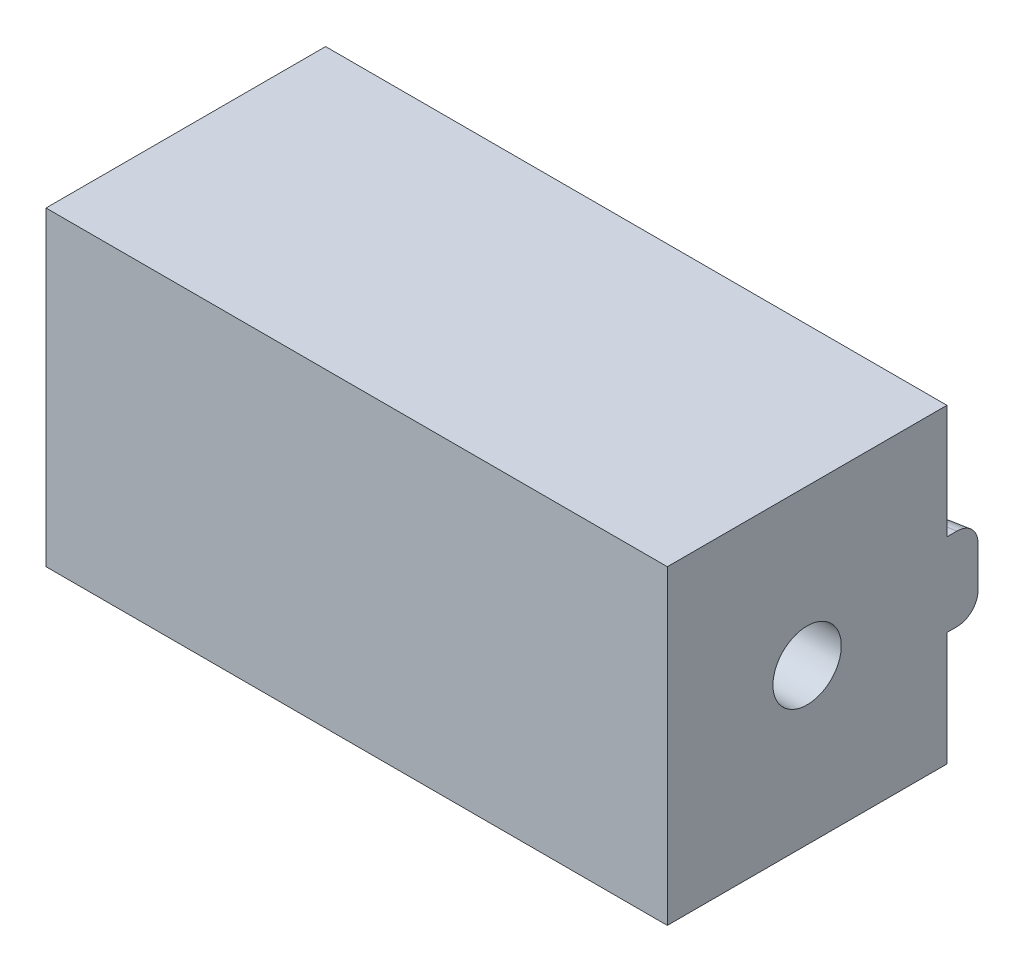
SolidWorks part; units mm, degrees
ref_plane "Top Plane" through (0, 0, 0) normal (0, 0, 1) x (1, 0, 0)
ref_plane "Right Plane" through (0, 0, 0) normal (0, 1, 0) x (1, 0, 0)
ref_plane "Front Plane" through (0, 0, 0) normal (1, 0, 0) x (0, 0, -1)
sketch "Sketch1" plane through (0, 0, 0) normal (0, 0, 1) x (1, 0, 0)
  line L1 (0, -7.5) -> (30, -7.5)
  line L2 (0, -7.5) -> (0, 7.5)
  line L3 (0, 7.5) -> (30, 7.5)
  line L4 (30, -7.5) -> (30, 7.5)
  dimension "D1" = 30
  dimension "D2" = 15
extrude "Boss-Extrude1" add sketch "Sketch1" along normal mid plane 13.5
sketch "Sketch2" plane through (0, 0, 0) normal (0, 1, 0) x (1, 0, 0)
  line L12 (0, 0) -> (30, 0) construction
  line L14 (30, 0) -> (30, 6.75) construction
  line L20 (0, 0) -> (30, 0)
  line L21 (0, 0) -> (0, 3)
  line L22 (0, 3) -> (22.5, 3)
  line L23 (22.5, 1.65) -> (22.5, 3)
  line L25 (30, 0) -> (30, 1.65)
  line L26 (30, 1.65) -> (22.5, 1.65)
  dimension "D1" = 7.5
  dimension "D2" = 3
  dimension "D3" = 1.65
sketch "Sketch3" plane through (0, -7.5, 0) normal (0, -1, 0) x (1, 0, 0)
  line L0 (0, 0) -> (30, 0) construction
  line L1 (0, 6.75) -> (0, -6.75) construction
  line L2 (30, 6.75) -> (30, -6.75) construction
  circle A0 centre (8, 0) radius 1.5
  circle A1 centre (23, 0) radius 1.5
  dimension "D1" = 3
  dimension "D2" = 7
  dimension "D3" = 15
extrude "Cut-Extrude1" cut sketch "Sketch3" against normal blind 3
sketch "Sketch4" plane through (0, 0, 0) normal (0, 1, 0) x (1, 0, 0)
  line L0 (30, 6.75) -> (30, 8.25)
  line L1 (30, 8.25) -> (22, 6.75)
  line L2 (22, 6.75) -> (30, 6.75)
  dimension "D1" = 15
  dimension "D2" = 8
extrude "Boss-Extrude2" add sketch "Sketch4" along normal mid plane 4
fillet "Fillet1" radius 1 2 edges at (26, 2, -7.5) (26, -2, -7.5)
revolve "Cut-Revolve1" cut sketch "Sketch2" angle 360 about L20
sketch "Sketch5" [suppressed] plane through (0, 0, 0) normal (0, 1, 0) x (1, 0, 0)
  line L0 (8.8, 3) -> (30, 3)
  line L1 (0, 0) -> (57, 0)
  line L2 (0, 0) -> (0, 3)
  line L3 (0, 3) -> (8.2, 3)
  line L4 (35, 1.5) -> (30, 3)
  line L7 (35, 1.5) -> (52, 1.5)
  line L8 (57, 0) -> (57, 1.3)
  line L11 (57, 1.3) -> (52, 1.3)
  line L12 (52, 1.5) -> (52, 1.3)
  arc A0 (8.8, 3) -> (8.2, 3) centre (8.5, 3) cw
  dimension "D7" = 0.3
  dimension "D1" = 3
  dimension "D2" = 57
  dimension "D3" = 30
  dimension "D4" = 1.5
  dimension "D5" = 0.2
  dimension "D6" = 5
  dimension "D8" = 8.5
  dimension "D9" = 22
revolve "Revolve1" [suppressed] add sketch "Sketch5" angle 360 about L1
fillet "Fillet2" [suppressed] radius 0.5
sketch "Sketch6" [suppressed] plane through (0, 0, 0) normal (0, 1, 0) x (1, 0, 0)
  line L0 (0, 0) -> (2.5, 0) construction
  circle A0 centre (2.5, 0) radius 1
  dimension "D1" = 2
  dimension "D2" = 2.5
extrude "Cut-Extrude2" [suppressed] cut sketch "Sketch6" against normal through all both and the other way through all
sketch "Sketch8" [suppressed] plane through (0, 0, 0) normal (0, 1, 0) x (1, 0, 0)
  line L1 (0, -3) -> (7, -3)
  line L2 (0, -3) -> (0, 3)
  line L3 (0, 3) -> (7, 3)
  line L4 (7, -3) -> (7, 3)
  dimension "D1" = 7
extrude "Cut-Extrude3" [suppressed] cut sketch "Sketch8" against normal mid plane 2
ref_axis "Axis1" [suppressed] through (52, 0, 0) along (-1, 0, 0)
